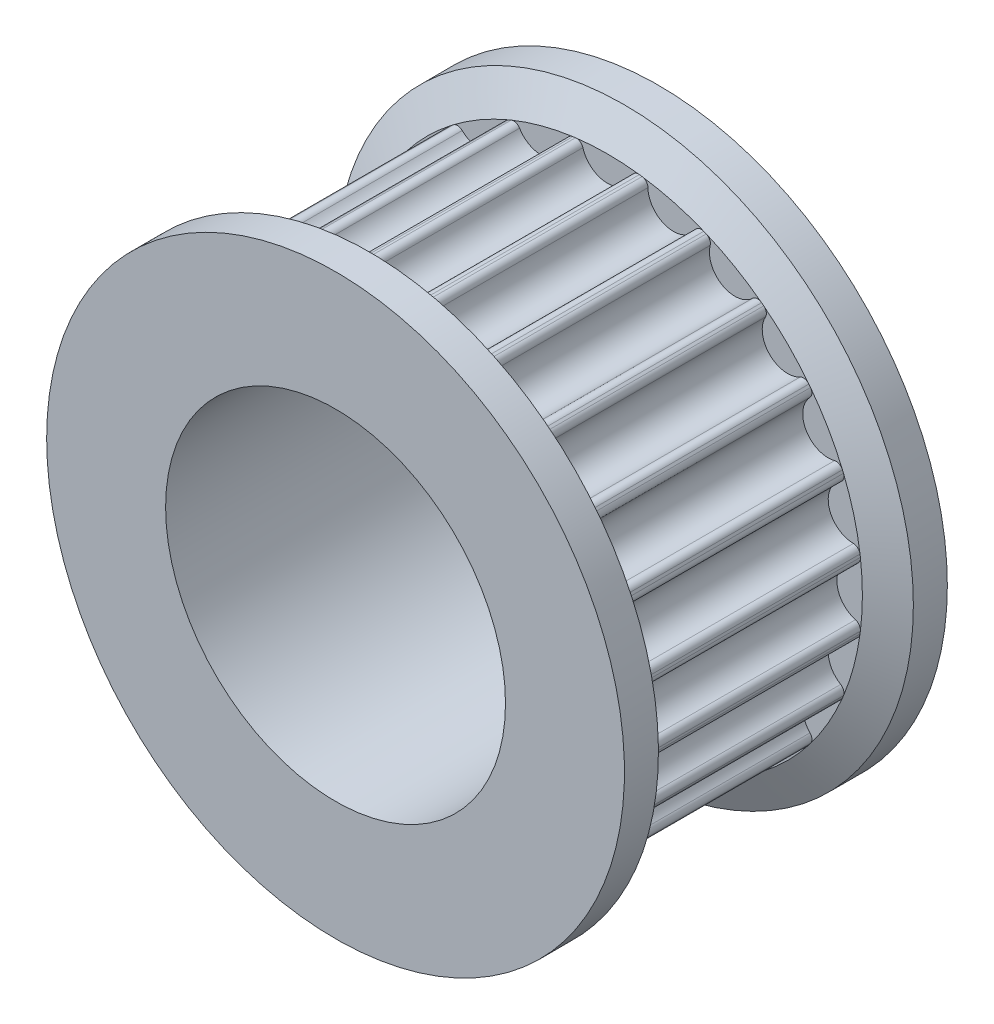
SolidWorks part; units mm, degrees
ref_plane "Front Plane" through (0, 0, 0) normal (0, 0, 1) x (1, 0, 0)
ref_plane "Top Plane" through (0, 0, 0) normal (0, 1, 0) x (1, 0, 0)
ref_plane "Right Plane" through (0, 0, 0) normal (1, 0, 0) x (0, 0, -1)
ref_plane "Plane1" through (0, 0, -263.25) normal (0, 0, 1) x (1, 0, 0)
sketch "Sketch1" plane through (0, 0, -263.25) normal (0, 0, 1) x (1, 0, 0)
  line L0 (-10.0202, 24.5147) -> (-9.9757, 24.3964) construction
  line L1 (-9.9757, 24.3964) -> (-9.9235, 24.2813) construction
  line L2 (-9.9235, 24.2813) -> (-9.8394, 24.2062) construction
  line L3 (-9.8394, 24.2062) -> (-9.728, 24.2042) construction
  line L4 (-9.728, 24.2042) -> (-9.6229, 24.2395) construction
  line L5 (-9.6229, 24.2395) -> (-9.5122, 24.2609) construction
  line L6 (-9.5122, 24.2609) -> (-9.3992, 24.2703) construction
  line L7 (-9.3992, 24.2703) -> (-9.2842, 24.2662) construction
  line L8 (-9.2842, 24.2662) -> (-9.1448, 24.2217) construction
  line L9 (-9.1448, 24.2217) -> (-9.0199, 24.1476) construction
  line L10 (-9.0199, 24.1476) -> (-8.9124, 24.0487) construction
  line L11 (-8.9124, 24.0487) -> (-8.827, 23.9292) construction
  line L12 (-8.827, 23.9292) -> (-8.7662, 23.7955) construction
  line L13 (-8.7662, 23.7955) -> (-8.7343, 23.653) construction
  line L14 (-8.7343, 23.653) -> (-8.7326, 23.5077) construction
  line L15 (-8.7326, 23.5077) -> (-8.7638, 23.3648) construction
  line L16 (-8.7638, 23.3648) -> (-8.8177, 23.2632) construction
  line L17 (-8.8177, 23.2632) -> (-8.8823, 23.17) construction
  line L18 (-8.8823, 23.17) -> (-8.9562, 23.0848) construction
  line L19 (-8.9562, 23.0848) -> (-8.9851, 23.1098) construction
  line L20 (-8.9851, 23.1098) -> (-9.0933, 22.9139) construction
  line L21 (-9.0933, 22.9139) -> (-9.0703, 22.8036) construction
  line L22 (-9.0703, 22.8036) -> (-8.9967, 22.7008) construction
  line L23 (-8.9967, 22.7008) -> (-8.9165, 22.6031) construction
  line L24 (-8.9165, 22.6031) -> (-8.8159, 22.5524) construction
  line L25 (-8.8159, 22.5524) -> (-8.7077, 22.5792) construction
  line L26 (-8.7077, 22.5792) -> (-8.6154, 22.6406) construction
  line L27 (-8.6154, 22.6406) -> (-8.5139, 22.6899) construction
  line L28 (-8.5139, 22.6899) -> (-8.4072, 22.7282) construction
  line L29 (-8.4072, 22.7282) -> (-8.2951, 22.754) construction
  line L30 (-8.2951, 22.754) -> (-8.1489, 22.7471) construction
  line L31 (-8.1489, 22.7471) -> (-8.0091, 22.7078) construction
  line L32 (-8.0091, 22.7078) -> (-7.8797, 22.6402) construction
  line L33 (-7.8797, 22.6402) -> (-7.7663, 22.5468) construction
  line L34 (-7.7663, 22.5468) -> (-7.6729, 22.4334) construction
  line L35 (-7.6729, 22.4334) -> (-7.6053, 22.304) construction
  line L36 (-7.6053, 22.304) -> (-7.566, 22.1642) construction
  line L37 (-7.566, 22.1642) -> (-7.5591, 22.018) construction
  line L38 (-7.5591, 22.018) -> (-7.5849, 21.9059) construction
  line L39 (-7.5849, 21.9059) -> (-7.6232, 21.7992) construction
  line L40 (-7.6232, 21.7992) -> (-7.6725, 21.6977) construction
  line L41 (-7.6725, 21.6977) -> (-7.7339, 21.6054) construction
  line L42 (-7.7339, 21.6054) -> (-7.7607, 21.4972) construction
  line L43 (-7.7607, 21.4972) -> (-7.7099, 21.3966) construction
  line L44 (-7.7099, 21.3966) -> (-7.6123, 21.3164) construction
  line L45 (-7.6123, 21.3164) -> (-7.5095, 21.2428) construction
  line L46 (-7.5095, 21.2428) -> (-7.3992, 21.2198) construction
  line L47 (-7.3992, 21.2198) -> (-7.2033, 21.328) construction
  line L48 (-7.2033, 21.328) -> (-7.2283, 21.3569) construction
  line L49 (-7.2283, 21.3569) -> (-7.1431, 21.4308) construction
  line L50 (-7.1431, 21.4308) -> (-7.0499, 21.4954) construction
  line L51 (-7.0499, 21.4954) -> (-6.9484, 21.5493) construction
  line L52 (-6.9484, 21.5493) -> (-6.8054, 21.5805) construction
  line L53 (-6.8054, 21.5805) -> (-6.6601, 21.5788) construction
  line L54 (-6.6601, 21.5788) -> (-6.5176, 21.5469) construction
  line L55 (-6.5176, 21.5469) -> (-6.3839, 21.4861) construction
  line L56 (-6.3839, 21.4861) -> (-6.2643, 21.4007) construction
  line L57 (-6.2643, 21.4007) -> (-6.1655, 21.2932) construction
  line L58 (-6.1655, 21.2932) -> (-6.0914, 21.1683) construction
  line L59 (-6.0914, 21.1683) -> (-6.0469, 21.0289) construction
  line L60 (-6.0469, 21.0289) -> (-6.0428, 20.914) construction
  line L61 (-6.0428, 20.914) -> (-6.0522, 20.8009) construction
  line L62 (-6.0522, 20.8009) -> (-6.0736, 20.6901) construction
  line L63 (-6.0736, 20.6901) -> (-6.109, 20.5851) construction
  line L64 (-6.109, 20.5851) -> (-6.1068, 20.4737) construction
  line L65 (-6.1068, 20.4737) -> (-6.0318, 20.3896) construction
  line L66 (-6.0318, 20.3896) -> (-5.9167, 20.3374) construction
  line L67 (-5.9167, 20.3374) -> (-5.7984, 20.2929) construction
  line L68 (-5.7984, 20.2929) -> (-5.6859, 20.2993) construction
  line L69 (-5.6859, 20.2993) -> (-5.6056, 20.3766) construction
  line L70 (-5.6056, 20.3766) -> (-5.5563, 20.4759) construction
  line L71 (-5.5563, 20.4759) -> (-5.4931, 20.5694) construction
  line L72 (-5.4931, 20.5694) -> (-5.4199, 20.6559) construction
  line L73 (-5.4199, 20.6559) -> (-5.3357, 20.7343) construction
  line L74 (-5.3357, 20.7343) -> (-5.2056, 20.8014) construction
  line L75 (-5.2056, 20.8014) -> (-5.0649, 20.8373) construction
  line L76 (-5.0649, 20.8373) -> (-4.919, 20.8434) construction
  line L77 (-4.919, 20.8434) -> (-4.7741, 20.8193) construction
  line L78 (-4.7741, 20.8193) -> (-4.6365, 20.7677) construction
  line L79 (-4.6365, 20.7677) -> (-4.5132, 20.6895) construction
  line L80 (-4.5132, 20.6895) -> (-4.4093, 20.588) construction
  line L81 (-4.4093, 20.588) -> (-4.3302, 20.4649) construction
  line L82 (-4.3302, 20.4649) -> (-4.2965, 20.3549) construction
  line L83 (-4.2965, 20.3549) -> (-4.2763, 20.2433) construction
  line L84 (-4.2763, 20.2433) -> (-4.2683, 20.1308) construction
  line L85 (-4.2683, 20.1308) -> (-4.2753, 20.0202) construction
  line L86 (-4.2753, 20.0202) -> (-4.2444, 19.9131) construction
  line L87 (-4.2444, 19.9131) -> (-4.1502, 19.8513) construction
  line L88 (-4.1502, 19.8513) -> (-4.0255, 19.8307) construction
  line L89 (-4.0255, 19.8307) -> (-3.8997, 19.8183) construction
  line L90 (-3.8997, 19.8183) -> (-3.7927, 19.8536) construction
  line L91 (-3.7927, 19.8536) -> (-3.7351, 19.9491) construction
  line L92 (-3.7351, 19.9491) -> (-3.7132, 20.0577) construction
  line L93 (-3.7132, 20.0577) -> (-3.6764, 20.1643) construction
  line L94 (-3.6764, 20.1643) -> (-3.628, 20.2669) construction
  line L95 (-3.628, 20.2669) -> (-3.567, 20.3644) construction
  line L96 (-3.567, 20.3644) -> (-3.4588, 20.4629) construction
  line L97 (-3.4588, 20.4629) -> (-3.3321, 20.534) construction
  line L98 (-3.3321, 20.534) -> (-3.1928, 20.5777) construction
  line L99 (-3.1928, 20.5777) -> (-3.0465, 20.5918) construction
  line L100 (-3.0465, 20.5918) -> (-2.9003, 20.5777) construction
  line L101 (-2.9003, 20.5777) -> (-2.761, 20.534) construction
  line L102 (-2.761, 20.534) -> (-2.6343, 20.4629) construction
  line L103 (-2.6343, 20.4629) -> (-2.5261, 20.3644) construction
  line L104 (-2.5261, 20.3644) -> (-2.4651, 20.2669) construction
  line L105 (-2.4651, 20.2669) -> (-2.4167, 20.1643) construction
  line L106 (-2.4167, 20.1643) -> (-2.3798, 20.0577) construction
  line L107 (-2.3798, 20.0577) -> (-2.358, 19.9491) construction
  line L108 (-2.358, 19.9491) -> (-2.3004, 19.8536) construction
  line L109 (-2.3004, 19.8536) -> (-2.1934, 19.8183) construction
  line L110 (-2.1934, 19.8183) -> (-2.0676, 19.8307) construction
  line L111 (-2.0676, 19.8307) -> (-1.9429, 19.8513) construction
  line L112 (-1.9429, 19.8513) -> (-1.8487, 19.9131) construction
  line L113 (-1.8487, 19.9131) -> (-1.8178, 20.0202) construction
  line L114 (-1.8178, 20.0202) -> (-1.8247, 20.1308) construction
  line L115 (-1.8247, 20.1308) -> (-1.8167, 20.2433) construction
  line L116 (-1.8167, 20.2433) -> (-1.7966, 20.3549) construction
  line L117 (-1.7966, 20.3549) -> (-1.7629, 20.4649) construction
  line L118 (-1.7629, 20.4649) -> (-1.6838, 20.588) construction
  line L119 (-1.6838, 20.588) -> (-1.5799, 20.6895) construction
  line L120 (-1.5799, 20.6895) -> (-1.4566, 20.7677) construction
  line L121 (-1.4566, 20.7677) -> (-1.319, 20.8193) construction
  line L122 (-1.319, 20.8193) -> (-1.1741, 20.8434) construction
  line L123 (-1.1741, 20.8434) -> (-1.0282, 20.8373) construction
  line L124 (-1.0282, 20.8373) -> (-0.8874, 20.8014) construction
  line L125 (-0.8874, 20.8014) -> (-0.7574, 20.7343) construction
  line L126 (-0.7574, 20.7343) -> (-0.6732, 20.6559) construction
  line L127 (-0.6732, 20.6559) -> (-0.6, 20.5694) construction
  line L128 (-0.6, 20.5694) -> (-0.5368, 20.4759) construction
  line L129 (-0.5368, 20.4759) -> (-0.4875, 20.3766) construction
  line L130 (-0.4875, 20.3766) -> (-0.4072, 20.2993) construction
  line L131 (-0.4072, 20.2993) -> (-0.2947, 20.2929) construction
  line L132 (-0.2947, 20.2929) -> (-0.1764, 20.3374) construction
  line L133 (-0.1764, 20.3374) -> (-0.0613, 20.3896) construction
  line L134 (-0.0613, 20.3896) -> (0.0138, 20.4737) construction
  line L135 (0.0138, 20.4737) -> (0.0159, 20.5851) construction
  line L136 (0.0159, 20.5851) -> (-0.0195, 20.6901) construction
  line L137 (-0.0195, 20.6901) -> (-0.0409, 20.8009) construction
  line L138 (-0.0409, 20.8009) -> (-0.0503, 20.914) construction
  line L139 (-0.0503, 20.914) -> (-0.0462, 21.0289) construction
  line L140 (-0.0462, 21.0289) -> (-0.0017, 21.1683) construction
  line L141 (-0.0017, 21.1683) -> (0.0724, 21.2932) construction
  line L142 (0.0724, 21.2932) -> (0.1713, 21.4007) construction
  line L143 (0.1713, 21.4007) -> (0.2908, 21.4861) construction
  line L144 (0.2908, 21.4861) -> (0.4245, 21.5469) construction
  line L145 (0.4245, 21.5469) -> (0.567, 21.5788) construction
  line L146 (0.567, 21.5788) -> (0.7123, 21.5805) construction
  line L147 (0.7123, 21.5805) -> (0.8553, 21.5493) construction
  line L148 (0.8553, 21.5493) -> (0.9569, 21.4954) construction
  line L149 (0.9569, 21.4954) -> (1.05, 21.4308) construction
  line L150 (1.05, 21.4308) -> (1.1353, 21.3569) construction
  line L151 (1.1353, 21.3569) -> (1.2085, 21.2737) construction
  line L152 (1.2085, 21.2737) -> (1.3061, 21.2198) construction
  line L153 (1.3061, 21.2198) -> (1.4165, 21.2428) construction
  line L154 (1.4165, 21.2428) -> (1.5192, 21.3164) construction
  line L155 (1.5192, 21.3164) -> (1.6169, 21.3966) construction
  line L156 (1.6169, 21.3966) -> (1.6676, 21.4972) construction
  line L157 (1.6676, 21.4972) -> (1.6408, 21.6054) construction
  line L158 (1.6408, 21.6054) -> (1.5794, 21.6977) construction
  line L159 (1.5794, 21.6977) -> (1.5301, 21.7992) construction
  line L160 (1.5301, 21.7992) -> (1.4918, 21.9059) construction
  line L161 (1.4918, 21.9059) -> (1.466, 22.018) construction
  line L162 (1.466, 22.018) -> (1.4729, 22.1642) construction
  line L163 (1.4729, 22.1642) -> (1.5122, 22.304) construction
  line L164 (1.5122, 22.304) -> (1.5798, 22.4334) construction
  line L165 (1.5798, 22.4334) -> (1.6732, 22.5468) construction
  line L166 (1.6732, 22.5468) -> (1.7866, 22.6402) construction
  line L167 (1.7866, 22.6402) -> (1.916, 22.7078) construction
  line L168 (1.916, 22.7078) -> (2.0558, 22.7471) construction
  line L169 (2.0558, 22.7471) -> (2.202, 22.754) construction
  line L170 (2.202, 22.754) -> (2.3141, 22.7282) construction
  line L171 (2.3141, 22.7282) -> (2.4208, 22.6899) construction
  line L172 (2.4208, 22.6899) -> (2.5223, 22.6406) construction
  line L173 (2.5223, 22.6406) -> (2.6146, 22.5792) construction
  line L174 (2.6146, 22.5792) -> (2.7228, 22.5524) construction
  line L175 (2.7228, 22.5524) -> (2.8235, 22.6031) construction
  line L176 (2.8235, 22.6031) -> (2.9036, 22.7008) construction
  line L177 (2.9036, 22.7008) -> (2.9772, 22.8036) construction
  line L178 (2.9772, 22.8036) -> (3.0002, 22.9139) construction
  line L179 (3.0002, 22.9139) -> (2.892, 23.1098) construction
  line L180 (2.892, 23.1098) -> (2.8632, 23.0848) construction
  line L181 (2.8632, 23.0848) -> (2.7892, 23.17) construction
  line L182 (2.7892, 23.17) -> (2.7246, 23.2632) construction
  line L183 (2.7246, 23.2632) -> (2.6707, 23.3648) construction
  line L184 (2.6707, 23.3648) -> (2.6395, 23.5077) construction
  line L185 (2.6395, 23.5077) -> (2.6413, 23.653) construction
  line L186 (2.6413, 23.653) -> (2.6731, 23.7955) construction
  line L187 (2.6731, 23.7955) -> (2.7339, 23.9292) construction
  line L188 (2.7339, 23.9292) -> (2.8193, 24.0487) construction
  line L189 (2.8193, 24.0487) -> (2.9268, 24.1476) construction
  line L190 (2.9268, 24.1476) -> (3.0517, 24.2217) construction
  line L191 (3.0517, 24.2217) -> (3.1911, 24.2662) construction
  line L192 (3.1911, 24.2662) -> (3.3061, 24.2703) construction
  line L193 (3.3061, 24.2703) -> (3.4191, 24.2609) construction
  line L194 (3.4191, 24.2609) -> (3.5298, 24.2395) construction
  line L195 (3.5298, 24.2395) -> (3.6349, 24.2042) construction
  line L196 (3.6349, 24.2042) -> (3.7463, 24.2062) construction
  line L197 (3.7463, 24.2062) -> (3.8304, 24.2813) construction
  line L198 (3.8304, 24.2813) -> (3.8826, 24.3964) construction
  line L199 (3.8826, 24.3964) -> (3.9271, 24.5147) construction
  line L200 (3.9271, 24.5147) -> (3.9207, 24.6272) construction
  line L201 (3.9207, 24.6272) -> (3.8434, 24.7075) construction
  line L202 (3.8434, 24.7075) -> (3.7441, 24.7568) construction
  line L203 (3.7441, 24.7568) -> (3.6507, 24.82) construction
  line L204 (3.6507, 24.82) -> (3.5641, 24.8932) construction
  line L205 (3.5641, 24.8932) -> (3.4857, 24.9774) construction
  line L206 (3.4857, 24.9774) -> (3.4186, 25.1075) construction
  line L207 (3.4186, 25.1075) -> (3.3827, 25.2482) construction
  line L208 (3.3827, 25.2482) -> (3.3766, 25.3941) construction
  line L209 (3.3766, 25.3941) -> (3.4007, 25.539) construction
  line L210 (3.4007, 25.539) -> (3.4523, 25.6766) construction
  line L211 (3.4523, 25.6766) -> (3.5305, 25.7999) construction
  line L212 (3.5305, 25.7999) -> (3.632, 25.9038) construction
  line L213 (3.632, 25.9038) -> (3.7551, 25.9829) construction
  line L214 (3.7551, 25.9829) -> (3.8651, 26.0166) construction
  line L215 (3.8651, 26.0166) -> (3.9767, 26.0368) construction
  line L216 (3.9767, 26.0368) -> (4.0892, 26.0448) construction
  line L217 (4.0892, 26.0448) -> (4.1998, 26.0378) construction
  line L218 (4.1998, 26.0378) -> (4.3069, 26.0687) construction
  line L219 (4.3069, 26.0687) -> (4.3687, 26.1629) construction
  line L220 (4.3687, 26.1629) -> (4.3893, 26.2876) construction
  line L221 (4.3893, 26.2876) -> (4.4017, 26.4134) construction
  line L222 (4.4017, 26.4134) -> (4.3664, 26.5204) construction
  line L223 (4.3664, 26.5204) -> (4.271, 26.578) construction
  line L224 (4.271, 26.578) -> (4.1623, 26.5998) construction
  line L225 (4.1623, 26.5998) -> (4.0557, 26.6367) construction
  line L226 (4.0557, 26.6367) -> (3.9531, 26.6851) construction
  line L227 (3.9531, 26.6851) -> (3.8556, 26.7461) construction
  line L228 (3.8556, 26.7461) -> (3.7571, 26.8543) construction
  line L229 (3.7571, 26.8543) -> (3.686, 26.981) construction
  line L230 (3.686, 26.981) -> (3.6424, 27.1203) construction
  line L231 (3.6424, 27.1203) -> (3.6281, 27.2665) construction
  line L232 (3.6281, 27.2665) -> (3.6424, 27.4128) construction
  line L233 (3.6424, 27.4128) -> (3.686, 27.5521) construction
  line L234 (3.686, 27.5521) -> (3.7571, 27.6788) construction
  line L235 (3.7571, 27.6788) -> (3.8556, 27.787) construction
  line L236 (3.8556, 27.787) -> (3.9531, 27.848) construction
  line L237 (3.9531, 27.848) -> (4.0557, 27.8964) construction
  line L238 (4.0557, 27.8964) -> (4.1623, 27.9333) construction
  line L239 (4.1623, 27.9333) -> (4.271, 27.9551) construction
  line L240 (4.271, 27.9551) -> (4.3664, 28.0127) construction
  line L241 (4.3664, 28.0127) -> (4.4017, 28.1197) construction
  line L242 (4.4017, 28.1197) -> (4.3893, 28.2455) construction
  line L243 (4.3893, 28.2455) -> (4.3687, 28.3702) construction
  line L244 (4.3687, 28.3702) -> (4.3069, 28.4645) construction
  line L245 (4.3069, 28.4645) -> (4.1998, 28.4954) construction
  line L246 (4.1998, 28.4954) -> (4.0892, 28.4884) construction
  line L247 (4.0892, 28.4884) -> (3.9767, 28.4963) construction
  line L248 (3.9767, 28.4963) -> (3.8651, 28.5165) construction
  line L249 (3.8651, 28.5165) -> (3.7551, 28.5502) construction
  line L250 (3.7551, 28.5502) -> (3.632, 28.6293) construction
  line L251 (3.632, 28.6293) -> (3.5305, 28.7332) construction
  line L252 (3.5305, 28.7332) -> (3.4523, 28.8565) construction
  line L253 (3.4523, 28.8565) -> (3.4007, 28.9941) construction
  line L254 (3.4007, 28.9941) -> (3.3766, 29.139) construction
  line L255 (3.3766, 29.139) -> (3.3827, 29.2849) construction
  line L256 (3.3827, 29.2849) -> (3.4186, 29.4256) construction
  line L257 (3.4186, 29.4256) -> (3.4857, 29.5557) construction
  line L258 (3.4857, 29.5557) -> (3.5641, 29.6399) construction
  line L259 (3.5641, 29.6399) -> (3.6507, 29.7131) construction
  line L260 (3.6507, 29.7131) -> (3.7441, 29.7763) construction
  line L261 (3.7441, 29.7763) -> (3.8434, 29.8256) construction
  line L262 (3.8434, 29.8256) -> (3.9207, 29.9059) construction
  line L263 (3.9207, 29.9059) -> (3.9271, 30.0184) construction
  line L264 (3.9271, 30.0184) -> (3.8826, 30.1367) construction
  line L265 (3.8826, 30.1367) -> (3.8304, 30.2518) construction
  line L266 (3.8304, 30.2518) -> (3.7463, 30.3268) construction
  line L267 (3.7463, 30.3268) -> (3.6349, 30.329) construction
  line L268 (3.6349, 30.329) -> (3.5298, 30.2936) construction
  line L269 (3.5298, 30.2936) -> (3.4191, 30.2722) construction
  line L270 (3.4191, 30.2722) -> (3.3061, 30.2628) construction
  line L271 (3.3061, 30.2628) -> (3.1911, 30.2669) construction
  line L272 (3.1911, 30.2669) -> (3.0517, 30.3114) construction
  line L273 (3.0517, 30.3114) -> (2.9268, 30.3855) construction
  line L274 (2.9268, 30.3855) -> (2.8193, 30.4843) construction
  line L275 (2.8193, 30.4843) -> (2.7339, 30.6039) construction
  line L276 (2.7339, 30.6039) -> (2.6731, 30.7376) construction
  line L277 (2.6731, 30.7376) -> (2.6413, 30.8801) construction
  line L278 (2.6413, 30.8801) -> (2.6395, 31.0254) construction
  line L279 (2.6395, 31.0254) -> (2.6707, 31.1684) construction
  line L280 (2.6707, 31.1684) -> (2.7246, 31.27) construction
  line L281 (2.7246, 31.27) -> (2.7892, 31.3631) construction
  line L282 (2.7892, 31.3631) -> (2.8632, 31.4484) construction
  line L283 (2.8632, 31.4484) -> (2.9463, 31.5216) construction
  line L284 (2.9463, 31.5216) -> (3.0002, 31.6192) construction
  line L285 (3.0002, 31.6192) -> (2.9772, 31.7296) construction
  line L286 (2.9772, 31.7296) -> (2.9036, 31.8323) construction
  line L287 (2.9036, 31.8323) -> (2.8235, 31.93) construction
  line L288 (2.8235, 31.93) -> (2.7228, 31.9807) construction
  line L289 (2.7228, 31.9807) -> (2.6146, 31.9539) construction
  line L290 (2.6146, 31.9539) -> (2.5223, 31.8926) construction
  line L291 (2.5223, 31.8926) -> (2.4208, 31.8432) construction
  line L292 (2.4208, 31.8432) -> (2.3141, 31.8049) construction
  line L293 (2.3141, 31.8049) -> (2.202, 31.7791) construction
  line L294 (2.202, 31.7791) -> (2.0558, 31.786) construction
  line L295 (2.0558, 31.786) -> (1.916, 31.8253) construction
  line L296 (1.916, 31.8253) -> (1.7866, 31.8929) construction
  line L297 (1.7866, 31.8929) -> (1.6732, 31.9863) construction
  line L298 (1.6732, 31.9863) -> (1.5798, 32.0997) construction
  line L299 (1.5798, 32.0997) -> (1.5122, 32.2291) construction
  line L300 (1.5122, 32.2291) -> (1.4729, 32.369) construction
  line L301 (1.4729, 32.369) -> (1.466, 32.5151) construction
  line L302 (1.466, 32.5151) -> (1.4918, 32.6272) construction
  line L303 (1.4918, 32.6272) -> (1.5301, 32.7339) construction
  line L304 (1.5301, 32.7339) -> (1.5794, 32.8354) construction
  line L305 (1.5794, 32.8354) -> (1.6408, 32.9277) construction
  line L306 (1.6408, 32.9277) -> (1.6676, 33.0359) construction
  line L307 (1.6676, 33.0359) -> (1.6169, 33.1366) construction
  line L308 (1.6169, 33.1366) -> (1.5192, 33.2167) construction
  line L309 (1.5192, 33.2167) -> (1.4165, 33.2903) construction
  line L310 (1.4165, 33.2903) -> (1.3061, 33.3133) construction
  line L311 (1.3061, 33.3133) -> (1.1102, 33.2051) construction
  line L312 (1.1102, 33.2051) -> (1.1353, 33.1762) construction
  line L313 (1.1353, 33.1762) -> (1.05, 33.1023) construction
  line L314 (1.05, 33.1023) -> (0.9569, 33.0377) construction
  line L315 (0.9569, 33.0377) -> (0.8553, 32.9838) construction
  line L316 (0.8553, 32.9838) -> (0.7123, 32.9526) construction
  line L317 (0.7123, 32.9526) -> (0.567, 32.9543) construction
  line L318 (0.567, 32.9543) -> (0.4245, 32.9862) construction
  line L319 (0.4245, 32.9862) -> (0.2908, 33.047) construction
  line L320 (0.2908, 33.047) -> (0.1713, 33.1324) construction
  line L321 (0.1713, 33.1324) -> (0.0724, 33.2399) construction
  line L322 (0.0724, 33.2399) -> (-0.0017, 33.3648) construction
  line L323 (-0.0017, 33.3648) -> (-0.0462, 33.5042) construction
  line L324 (-0.0462, 33.5042) -> (-0.0503, 33.6192) construction
  line L325 (-0.0503, 33.6192) -> (-0.0409, 33.7322) construction
  line L326 (-0.0409, 33.7322) -> (-0.0195, 33.8429) construction
  line L327 (-0.0195, 33.8429) -> (0.0159, 33.948) construction
  line L328 (0.0159, 33.948) -> (0.0138, 34.0595) construction
  line L329 (0.0138, 34.0595) -> (-0.0613, 34.1435) construction
  line L330 (-0.0613, 34.1435) -> (-0.1764, 34.1956) construction
  line L331 (-0.1764, 34.1956) -> (-0.2947, 34.2402) construction
  line L332 (-0.2947, 34.2402) -> (-0.4072, 34.2338) construction
  line L333 (-0.4072, 34.2338) -> (-0.4875, 34.1565) construction
  line L334 (-0.4875, 34.1565) -> (-0.5368, 34.0572) construction
  line L335 (-0.5368, 34.0572) -> (-0.6, 33.9638) construction
  line L336 (-0.6, 33.9638) -> (-0.6732, 33.8772) construction
  line L337 (-0.6732, 33.8772) -> (-0.7574, 33.7988) construction
  line L338 (-0.7574, 33.7988) -> (-0.8874, 33.7317) construction
  line L339 (-0.8874, 33.7317) -> (-1.0282, 33.6958) construction
  line L340 (-1.0282, 33.6958) -> (-1.1741, 33.6897) construction
  line L341 (-1.1741, 33.6897) -> (-1.319, 33.7138) construction
  line L342 (-1.319, 33.7138) -> (-1.4566, 33.7654) construction
  line L343 (-1.4566, 33.7654) -> (-1.5799, 33.8436) construction
  line L344 (-1.5799, 33.8436) -> (-1.6838, 33.9451) construction
  line L345 (-1.6838, 33.9451) -> (-1.7629, 34.0682) construction
  line L346 (-1.7629, 34.0682) -> (-1.7966, 34.1782) construction
  line L347 (-1.7966, 34.1782) -> (-1.8167, 34.2898) construction
  line L348 (-1.8167, 34.2898) -> (-1.8247, 34.4023) construction
  line L349 (-1.8247, 34.4023) -> (-1.8178, 34.5129) construction
  line L350 (-1.8178, 34.5129) -> (-1.8487, 34.62) construction
  line L351 (-1.8487, 34.62) -> (-1.9429, 34.6818) construction
  line L352 (-1.9429, 34.6818) -> (-2.0676, 34.7024) construction
  line L353 (-2.0676, 34.7024) -> (-2.1934, 34.7148) construction
  line L354 (-2.1934, 34.7148) -> (-2.3004, 34.6795) construction
  line L355 (-2.3004, 34.6795) -> (-2.358, 34.5841) construction
  line L356 (-2.358, 34.5841) -> (-2.3798, 34.4754) construction
  line L357 (-2.3798, 34.4754) -> (-2.4167, 34.3688) construction
  line L358 (-2.4167, 34.3688) -> (-2.4651, 34.2662) construction
  line L359 (-2.4651, 34.2662) -> (-2.5261, 34.1687) construction
  line L360 (-2.5261, 34.1687) -> (-2.6343, 34.0702) construction
  line L361 (-2.6343, 34.0702) -> (-2.761, 33.9991) construction
  line L362 (-2.761, 33.9991) -> (-2.9003, 33.9554) construction
  line L363 (-2.9003, 33.9554) -> (-3.0465, 33.9412) construction
  line L364 (-3.0465, 33.9412) -> (-3.1928, 33.9554) construction
  line L365 (-3.1928, 33.9554) -> (-3.3321, 33.9991) construction
  line L366 (-3.3321, 33.9991) -> (-3.4588, 34.0702) construction
  line L367 (-3.4588, 34.0702) -> (-3.567, 34.1687) construction
  line L368 (-3.567, 34.1687) -> (-3.628, 34.2662) construction
  line L369 (-3.628, 34.2662) -> (-3.6764, 34.3688) construction
  line L370 (-3.6764, 34.3688) -> (-3.7132, 34.4754) construction
  line L371 (-3.7132, 34.4754) -> (-3.7351, 34.5841) construction
  line L372 (-3.7351, 34.5841) -> (-3.7927, 34.6795) construction
  line L373 (-3.7927, 34.6795) -> (-3.8997, 34.7148) construction
  line L374 (-3.8997, 34.7148) -> (-4.0255, 34.7024) construction
  line L375 (-4.0255, 34.7024) -> (-4.1502, 34.6818) construction
  line L376 (-4.1502, 34.6818) -> (-4.2444, 34.62) construction
  line L377 (-4.2444, 34.62) -> (-4.2753, 34.5129) construction
  line L378 (-4.2753, 34.5129) -> (-4.2683, 34.4023) construction
  line L379 (-4.2683, 34.4023) -> (-4.2763, 34.2898) construction
  line L380 (-4.2763, 34.2898) -> (-4.2965, 34.1782) construction
  line L381 (-4.2965, 34.1782) -> (-4.3302, 34.0682) construction
  line L382 (-4.3302, 34.0682) -> (-4.4093, 33.9451) construction
  line L383 (-4.4093, 33.9451) -> (-4.5132, 33.8436) construction
  line L384 (-4.5132, 33.8436) -> (-4.6365, 33.7654) construction
  line L385 (-4.6365, 33.7654) -> (-4.7741, 33.7138) construction
  line L386 (-4.7741, 33.7138) -> (-4.919, 33.6897) construction
  line L387 (-4.919, 33.6897) -> (-5.0649, 33.6958) construction
  line L388 (-5.0649, 33.6958) -> (-5.2056, 33.7317) construction
  line L389 (-5.2056, 33.7317) -> (-5.3357, 33.7988) construction
  line L390 (-5.3357, 33.7988) -> (-5.4199, 33.8772) construction
  line L391 (-5.4199, 33.8772) -> (-5.4931, 33.9638) construction
  line L392 (-5.4931, 33.9638) -> (-5.5563, 34.0572) construction
  line L393 (-5.5563, 34.0572) -> (-5.6056, 34.1565) construction
  line L394 (-5.6056, 34.1565) -> (-5.6859, 34.2338) construction
  line L395 (-5.6859, 34.2338) -> (-5.7984, 34.2402) construction
  line L396 (-5.7984, 34.2402) -> (-5.9167, 34.1956) construction
  line L397 (-5.9167, 34.1956) -> (-6.0318, 34.1435) construction
  line L398 (-6.0318, 34.1435) -> (-6.1068, 34.0595) construction
  line L399 (-6.1068, 34.0595) -> (-6.109, 33.948) construction
  line L400 (-6.109, 33.948) -> (-6.0736, 33.8429) construction
  line L401 (-6.0736, 33.8429) -> (-6.0522, 33.7322) construction
  line L402 (-6.0522, 33.7322) -> (-6.0428, 33.6192) construction
  line L403 (-6.0428, 33.6192) -> (-6.0469, 33.5042) construction
  line L404 (-6.0469, 33.5042) -> (-6.0914, 33.3648) construction
  line L405 (-6.0914, 33.3648) -> (-6.1655, 33.2399) construction
  line L406 (-6.1655, 33.2399) -> (-6.2643, 33.1324) construction
  line L407 (-6.2643, 33.1324) -> (-6.3839, 33.047) construction
  line L408 (-6.3839, 33.047) -> (-6.5176, 32.9862) construction
  line L409 (-6.5176, 32.9862) -> (-6.6601, 32.9543) construction
  line L410 (-6.6601, 32.9543) -> (-6.8054, 32.9526) construction
  line L411 (-6.8054, 32.9526) -> (-6.9484, 32.9838) construction
  line L412 (-6.9484, 32.9838) -> (-7.0499, 33.0377) construction
  line L413 (-7.0499, 33.0377) -> (-7.1431, 33.1023) construction
  line L414 (-7.1431, 33.1023) -> (-7.2283, 33.1762) construction
  line L415 (-7.2283, 33.1762) -> (-7.2033, 33.2051) construction
  line L416 (-7.2033, 33.2051) -> (-7.3992, 33.3133) construction
  line L417 (-7.3992, 33.3133) -> (-7.5095, 33.2903) construction
  line L418 (-7.5095, 33.2903) -> (-7.6123, 33.2167) construction
  line L419 (-7.6123, 33.2167) -> (-7.7099, 33.1366) construction
  line L420 (-7.7099, 33.1366) -> (-7.7607, 33.0359) construction
  line L421 (-7.7607, 33.0359) -> (-7.7339, 32.9277) construction
  line L422 (-7.7339, 32.9277) -> (-7.6725, 32.8354) construction
  line L423 (-7.6725, 32.8354) -> (-7.6232, 32.7339) construction
  line L424 (-7.6232, 32.7339) -> (-7.5849, 32.6272) construction
  line L425 (-7.5849, 32.6272) -> (-7.5591, 32.5151) construction
  line L426 (-7.5591, 32.5151) -> (-7.566, 32.369) construction
  line L427 (-7.566, 32.369) -> (-7.6053, 32.2291) construction
  line L428 (-7.6053, 32.2291) -> (-7.6729, 32.0997) construction
  line L429 (-7.6729, 32.0997) -> (-7.7663, 31.9863) construction
  line L430 (-7.7663, 31.9863) -> (-7.8797, 31.8929) construction
  line L431 (-7.8797, 31.8929) -> (-8.0091, 31.8253) construction
  line L432 (-8.0091, 31.8253) -> (-8.1489, 31.786) construction
  line L433 (-8.1489, 31.786) -> (-8.2951, 31.7791) construction
  line L434 (-8.2951, 31.7791) -> (-8.4072, 31.8049) construction
  line L435 (-8.4072, 31.8049) -> (-8.5139, 31.8432) construction
  line L436 (-8.5139, 31.8432) -> (-8.6154, 31.8926) construction
  line L437 (-8.6154, 31.8926) -> (-8.7077, 31.9539) construction
  line L438 (-8.7077, 31.9539) -> (-8.8159, 31.9807) construction
  line L439 (-8.8159, 31.9807) -> (-8.9165, 31.93) construction
  line L440 (-8.9165, 31.93) -> (-8.9967, 31.8323) construction
  line L441 (-8.9967, 31.8323) -> (-9.0703, 31.7296) construction
  line L442 (-9.0703, 31.7296) -> (-9.0933, 31.6192) construction
  line L443 (-9.0933, 31.6192) -> (-8.9851, 31.4233) construction
  line L444 (-8.9851, 31.4233) -> (-8.9562, 31.4484) construction
  line L445 (-8.9562, 31.4484) -> (-8.8823, 31.3631) construction
  line L446 (-8.8823, 31.3631) -> (-8.8177, 31.27) construction
  line L447 (-8.8177, 31.27) -> (-8.7638, 31.1684) construction
  line L448 (-8.7638, 31.1684) -> (-8.7326, 31.0254) construction
  line L449 (-8.7326, 31.0254) -> (-8.7343, 30.8801) construction
  line L450 (-8.7343, 30.8801) -> (-8.7662, 30.7376) construction
  line L451 (-8.7662, 30.7376) -> (-8.827, 30.6039) construction
  line L452 (-8.827, 30.6039) -> (-8.9124, 30.4843) construction
  line L453 (-8.9124, 30.4843) -> (-9.0199, 30.3855) construction
  line L454 (-9.0199, 30.3855) -> (-9.1448, 30.3114) construction
  line L455 (-9.1448, 30.3114) -> (-9.2842, 30.2669) construction
  line L456 (-9.2842, 30.2669) -> (-9.3992, 30.2628) construction
  line L457 (-9.3992, 30.2628) -> (-9.5122, 30.2722) construction
  line L458 (-9.5122, 30.2722) -> (-9.6229, 30.2936) construction
  line L459 (-9.6229, 30.2936) -> (-9.728, 30.329) construction
  line L460 (-9.728, 30.329) -> (-9.8394, 30.3268) construction
  line L461 (-9.8394, 30.3268) -> (-9.9235, 30.2518) construction
  line L462 (-9.9235, 30.2518) -> (-9.9757, 30.1367) construction
  line L463 (-9.9757, 30.1367) -> (-10.0202, 30.0184) construction
  line L464 (-10.0202, 30.0184) -> (-10.0138, 29.9059) construction
  line L465 (-10.0138, 29.9059) -> (-9.9365, 29.8256) construction
  line L466 (-9.9365, 29.8256) -> (-9.8372, 29.7763) construction
  line L467 (-9.8372, 29.7763) -> (-9.7437, 29.7131) construction
  line L468 (-9.7437, 29.7131) -> (-9.6572, 29.6399) construction
  line L469 (-9.6572, 29.6399) -> (-9.5788, 29.5557) construction
  line L470 (-9.5788, 29.5557) -> (-9.5117, 29.4256) construction
  line L471 (-9.5117, 29.4256) -> (-9.4758, 29.2849) construction
  line L472 (-9.4758, 29.2849) -> (-9.4697, 29.139) construction
  line L473 (-9.4697, 29.139) -> (-9.4938, 28.9941) construction
  line L474 (-9.4938, 28.9941) -> (-9.5454, 28.8565) construction
  line L475 (-9.5454, 28.8565) -> (-9.6236, 28.7332) construction
  line L476 (-9.6236, 28.7332) -> (-9.7251, 28.6293) construction
  line L477 (-9.7251, 28.6293) -> (-9.8482, 28.5502) construction
  line L478 (-9.8482, 28.5502) -> (-9.9582, 28.5165) construction
  line L479 (-9.9582, 28.5165) -> (-10.0698, 28.4963) construction
  line L480 (-10.0698, 28.4963) -> (-10.1823, 28.4884) construction
  line L481 (-10.1823, 28.4884) -> (-10.2929, 28.4954) construction
  line L482 (-10.2929, 28.4954) -> (-10.4, 28.4645) construction
  line L483 (-10.4, 28.4645) -> (-10.4618, 28.3702) construction
  line L484 (-10.4618, 28.3702) -> (-10.4824, 28.2455) construction
  line L485 (-10.4824, 28.2455) -> (-10.4948, 28.1197) construction
  line L486 (-10.4948, 28.1197) -> (-10.4595, 28.0127) construction
  line L487 (-10.4595, 28.0127) -> (-10.364, 27.9551) construction
  line L488 (-10.364, 27.9551) -> (-10.2554, 27.9333) construction
  line L489 (-10.2554, 27.9333) -> (-10.1488, 27.8964) construction
  line L490 (-10.1488, 27.8964) -> (-10.0462, 27.848) construction
  line L491 (-10.0462, 27.848) -> (-9.9487, 27.787) construction
  line L492 (-9.9487, 27.787) -> (-9.8502, 27.6788) construction
  line L493 (-9.8502, 27.6788) -> (-9.7791, 27.5521) construction
  line L494 (-9.7791, 27.5521) -> (-9.7354, 27.4128) construction
  line L495 (-9.7354, 27.4128) -> (-9.7212, 27.2665) construction
  line L496 (-9.7212, 27.2665) -> (-9.7354, 27.1203) construction
  line L497 (-9.7354, 27.1203) -> (-9.7791, 26.981) construction
  line L498 (-9.7791, 26.981) -> (-9.8502, 26.8543) construction
  line L499 (-9.8502, 26.8543) -> (-9.9487, 26.7461) construction
  line L500 (-9.9487, 26.7461) -> (-10.0462, 26.6851) construction
  line L501 (-10.0462, 26.6851) -> (-10.1488, 26.6367) construction
  line L502 (-10.1488, 26.6367) -> (-10.2554, 26.5998) construction
  line L503 (-10.2554, 26.5998) -> (-10.364, 26.578) construction
  line L504 (-10.364, 26.578) -> (-10.4595, 26.5204) construction
  line L505 (-10.4595, 26.5204) -> (-10.4948, 26.4134) construction
  line L506 (-10.4948, 26.4134) -> (-10.4824, 26.2876) construction
  line L507 (-10.4824, 26.2876) -> (-10.4618, 26.1629) construction
  line L508 (-10.4618, 26.1629) -> (-10.4, 26.0687) construction
  line L509 (-10.4, 26.0687) -> (-10.2929, 26.0378) construction
  line L510 (-10.2929, 26.0378) -> (-10.1823, 26.0448) construction
  line L511 (-10.1823, 26.0448) -> (-10.0698, 26.0368) construction
  line L512 (-10.0698, 26.0368) -> (-9.9582, 26.0166) construction
  line L513 (-9.9582, 26.0166) -> (-9.8482, 25.9829) construction
  line L514 (-9.8482, 25.9829) -> (-9.7251, 25.9038) construction
  line L515 (-9.7251, 25.9038) -> (-9.6236, 25.7999) construction
  line L516 (-9.6236, 25.7999) -> (-9.5454, 25.6766) construction
  line L517 (-9.5454, 25.6766) -> (-9.4938, 25.539) construction
  line L518 (-9.4938, 25.539) -> (-9.4697, 25.3941) construction
  line L519 (-9.4697, 25.3941) -> (-9.4758, 25.2482) construction
  line L520 (-9.4758, 25.2482) -> (-9.5117, 25.1075) construction
  line L521 (-9.5117, 25.1075) -> (-9.5788, 24.9774) construction
  line L522 (-9.5788, 24.9774) -> (-9.6572, 24.8932) construction
  line L523 (-9.6572, 24.8932) -> (-9.7437, 24.82) construction
  line L524 (-9.7437, 24.82) -> (-9.8372, 24.7568) construction
  line L525 (-9.8372, 24.7568) -> (-9.9365, 24.7075) construction
  line L526 (-9.9365, 24.7075) -> (-10.0138, 24.6272) construction
  line L527 (-10.0138, 24.6272) -> (-10.0202, 24.5147) construction
  line L528 (-4.0255, 34.7024) -> (-2.0676, 19.8307) construction
  circle A0 centre (-3.0465, 27.2666) radius 7.5
  circle A1 centre (-3.0465, 34.7666) radius 0.75 construction
  dimension "D1" = 15
  dimension "D2" = 1.5
extrude "Boss-Extrude1" add sketch "Sketch1" against normal blind 7.5
ref_plane "Plane2" through (0, 0, -270.75) normal (0, 0, 1) x (1, 0, 0)
sketch "Sketch2" plane through (0, 0, -270.75) normal (0, 0, 1) x (1, 0, 0)
  circle A0 centre (-3.0465, 27.2666) radius 8.5
  dimension "D1" = 17
extrude "Boss-Extrude2" add sketch "Sketch2" against normal blind 1
ref_plane "Plane3" through (0, 0, -263.25) normal (0, 0, -1) x (-1, 0, 0)
sketch "Sketch3" plane through (0, 0, -263.25) normal (0, 0, -1) x (-1, 0, 0)
  circle A0 centre (3.0465, 27.2666) radius 8.5
  dimension "D1" = 17
extrude "Boss-Extrude3" add sketch "Sketch3" against normal blind 1
sketch "Sketch6" plane through (0, 0, -270.75) normal (0, 0, 1) x (1, 0, 0)
  circle A0 centre (-3.0465, 27.2666) radius 7.5 construction
  circle A1 centre (-3.0465, 27.2666) radius 7.5 construction
  circle A2 centre (-3.0465, 34.7666) radius 0.75
  circle A3 centre (-1.1054, 34.511) radius 0.75
  circle A4 centre (0.7035, 33.7617) radius 0.75
  circle A5 centre (2.2568, 32.5699) radius 0.75
  circle A6 centre (3.4486, 31.0166) radius 0.75
  circle A7 centre (4.1979, 29.2077) radius 0.75
  circle A8 centre (4.4535, 27.2666) radius 0.75
  circle A9 centre (4.1979, 25.3254) radius 0.75
  circle A10 centre (3.4486, 23.5166) radius 0.75
  circle A11 centre (2.2568, 21.9633) radius 0.75
  circle A12 centre (0.7035, 20.7714) radius 0.75
  circle A13 centre (-1.1054, 20.0221) radius 0.75
  circle A14 centre (-3.0465, 19.7666) radius 0.75
  circle A15 centre (-4.9877, 20.0221) radius 0.75
  circle A16 centre (-6.7965, 20.7714) radius 0.75
  circle A17 centre (-8.3498, 21.9633) radius 0.75
  circle A18 centre (-9.5417, 23.5166) radius 0.75
  circle A19 centre (-10.291, 25.3254) radius 0.75
  circle A20 centre (-10.5465, 27.2666) radius 0.75
  circle A21 centre (-10.291, 29.2077) radius 0.75
  circle A22 centre (-9.5417, 31.0166) radius 0.75
  circle A23 centre (-8.3498, 32.5699) radius 0.75
  circle A24 centre (-6.7965, 33.7617) radius 0.75
  circle A25 centre (-4.9877, 34.511) radius 0.75
  point P53 (-3.0465, 27.2666)
  dimension "D1" = 1.5
  dimension "D2" = 24
extrude "Cut-Extrude3" cut sketch "Sketch6" along normal blind 6.5 from offset 0.5
sketch "Sketch4" plane through (0, 0, -262.25) normal (0, 0, 1) x (1, 0, 0)
  circle A0 centre (-3.0465, 27.2666) radius 5
  dimension "D1" = 10
extrude "Cut-Extrude1" cut sketch "Sketch4" against normal blind 8
sketch "Sketch5" plane through (0, 0, -270.25) normal (0, 0, 1) x (1, 0, 0)
  circle A0 centre (-3.0465, 27.2666) radius 3.75
  dimension "D1" = 7.5
extrude "Cut-Extrude2" cut sketch "Sketch5" against normal through all
chamfer "Chamfer1" distance 0.5 distance2 1 1 edges at (4.4535, 27.2666, -270.75) first distance on face at (-4.9828, 34.4929, -267)
chamfer "Chamfer2" distance 0.5 distance2 1 1 edges at (4.4535, 27.2666, -263.25) first distance on face at (-3.0465, 27.2666, -267)
fillet "Fillet2" radius 0.2 48 edges at (-10.509, 26.5175, -267) (-10.4486, 26.0587, -267) (-10.509, 28.0156, -267) (-10.4486, 28.4745, -267) (-10.0609, 29.9215, -267) (-9.8838, 30.3491, -267) (-9.1347, 31.6465, -267) (-8.853, 32.0137, -267) (-7.7937, 33.073, -267) (-7.4265, 33.3547, -267) (-6.1291, 34.1038, -267) (-5.7015, 34.2809, -267) (-4.2544, 34.6687, -267) (-3.7956, 34.7291, -267) (-2.2975, 34.7291, -267) (-1.8386, 34.6687, -267) (-0.3916, 34.2809, -267) (0.036, 34.1038, -267) (1.3334, 33.3547, -267) (1.7006, 33.073, -267) (2.7599, 32.0137, -267) (3.0416, 31.6465, -267) (3.7907, 30.3491, -267) (3.9678, 29.9215, -267) (4.3556, 28.4745, -267) (4.416, 28.0156, -267) (4.416, 26.5175, -267) (4.3556, 26.0587, -267) (3.9678, 24.6116, -267) (3.7907, 24.184, -267) (3.0416, 22.8866, -267) (2.7599, 22.5194, -267) (1.7006, 21.4601, -267) (1.3334, 21.1784, -267) (0.036, 20.4293, -267) (-0.3916, 20.2522, -267) (-1.8386, 19.8645, -267) (-2.2975, 19.8041, -267) (-3.7956, 19.8041, -267) (-4.2544, 19.8645, -267) (-5.7015, 20.2522, -267) (-6.1291, 20.4293, -267) (-7.4265, 21.1784, -267) (-7.7937, 21.4601, -267) (-8.853, 22.5194, -267) (-9.1347, 22.8866, -267) (-9.8838, 24.184, -267) (-10.0609, 24.6116, -267)
